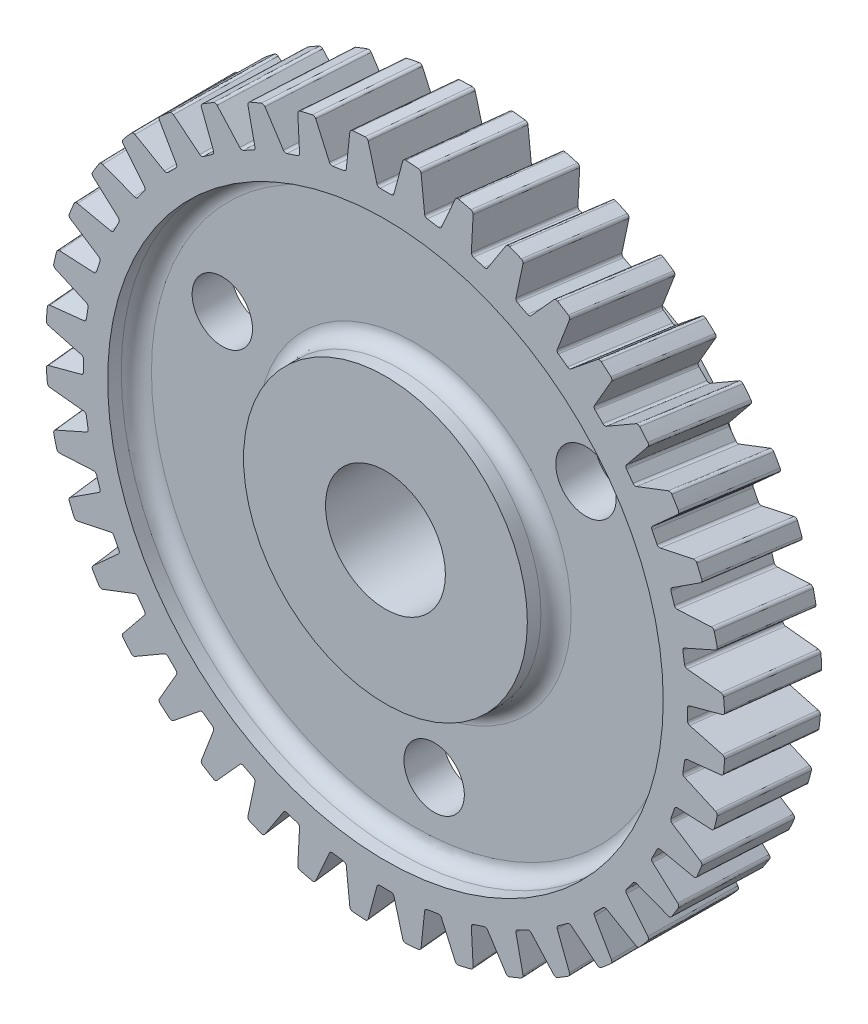
SolidWorks part; units mm, degrees
ref_plane "Front Plane" through (0, 0, 0) normal (0, 0, 1) x (1, 0, 0)
ref_plane "Top Plane" through (0, 0, 0) normal (0, 1, 0) x (1, 0, 0)
ref_plane "Right Plane" through (0, 0, 0) normal (1, 0, 0) x (0, 0, -1)
sketch "Sketch2" plane through (0, 0, 0) normal (1, 0, 0) x (0, 0, -1)
  line L0 (0, 0) -> (0, 22.5) construction
  line L1 (11, 3.9688) -> (-3.2, 3.9687)
  line L2 (-3.2, 3.9687) -> (-3.2, 9.4)
  line L3 (-3.2, 9.4) -> (-1.3, 9.4)
  line L4 (-1.3, 9.4) -> (-1.3, 18.4)
  line L5 (-1.3, 18.4) -> (-3.2, 18.4)
  line L6 (-3.2, 18.4) -> (-3.2, 22.5)
  line L7 (-3.2, 22.5) -> (3.2, 22.5)
  line L8 (3.2, 18.4) -> (3.2, 22.5)
  line L9 (1.3, 18.4) -> (3.2, 18.4)
  line L10 (1.3, 9.4) -> (1.3, 18.4)
  line L11 (3.2, 9.4) -> (1.3, 9.4)
  line L12 (3.2, 9.4) -> (11, 9.4)
  line L13 (11, 9.4) -> (11, 3.9688)
  line L14 (0, 0) -> (14.174, 0) construction
  dimension "D1" = 14.2
  dimension "D2" = 3.2
  dimension "D3" = 4.5
  dimension "D4" = 7.9375
  dimension "D5" = 9.4
  dimension "D6" = 9
  dimension "D7" = 22.5
  dimension "D8" = 6.4
revolve "Revolve1" add sketch "Sketch2" angle 360 about L14
fillet "Fillet1" radius 1 4 edges at (18.4, 0, 1.3) (9.4, 0, 1.3) (9.4, 0, -1.3) (18.4, 0, -1.3)
sketch "Sketch3" plane through (0, 0, 3.2) normal (0, 0, 1) x (1, 0, 0)
  line L0 (0, 22.6922) -> (0, 20) construction
  line L1 (-0.525, 20) -> (0.525, 20)
  line L2 (0.525, 20) -> (1.2464, 22.6922)
  line L3 (1.2464, 22.6922) -> (-1.2464, 22.6922)
  line L4 (-0.525, 20) -> (-1.2464, 22.6922)
  dimension "D1" = 20
  dimension "D2" = 1.05
  dimension "D3" = 15
sketch "Sketch4" plane through (0, 0, 0) normal (0, 1, 0) x (1, 0, 0)
  line L0 (0, -3.2) -> (0.691, 3.2)
  line L1 (1.2464, -3.2) -> (-1.2464, -3.2) construction
  line L2 (22.5, 3.2) -> (-22.5, 3.2) construction
sweep "Cut-Sweep1" cut profiles "Sketch3" path "Sketch4"
pattern_circular "CirPattern1" count 40 over 360 about axis through (0, 0, 3.2) along (0, 0, 1) of "Cut-Sweep1"
fillet "Fillet2" radius 0.2 160 edges at (1.526, 22.4482, 0.0047) (0.8705, 20, 0) (-0.8445, 22.4841, -0.0056) (-2.0045, 22.4105, 0.0047) (-2.2689, 19.8899, 0) (-3.306, 19.7257, 0) (-4.3514, 22.0752, -0.0056) (-5.4856, 21.8211, 0.0047) (-5.3525, 19.2901, 0) (-6.3511, 18.9657, 0) (-7.7512, 21.1227, -0.0056) (-8.8316, 20.6943, 0.0047) (-8.3042, 18.2153, 0) (-9.2398, 17.7386, 0) (-10.9601, 19.6501, -0.0056) (-11.9602, 19.0579, 0.0047) (-11.0515, 16.692, 0) (-11.9009, 16.0748, 0) (-13.8991, 17.6936, -0.0056) (-14.7943, 16.9523, 0.0047) (-13.5266, 14.7577, 0) (-14.2691, 14.0152, 0) (-16.4959, 15.3015, -0.0056) (-17.264, 14.4292, 0.0047) (-15.6687, 12.4599, 0) (-16.2859, 11.6105, 0) (-18.6865, 12.5326, -0.0056) (-19.3087, 11.5509, 0.0047) (-17.4249, 9.8554, 0) (-17.9016, 8.9199, 0) (-20.4169, 9.4551, -0.0056) (-20.878, 8.3882, 0.0047) (-18.7521, 7.0082, 0) (-19.0766, 6.0096, 0) (-21.6447, 6.1448, -0.0056) (-21.9331, 5.0188, 0.0047) (-19.6176, 3.9885, 0) (-19.7818, 2.9514, 0) (-22.3394, 2.6832, -0.0056) (-22.4482, 1.526, 0.0047) (-20, 0.8705, 0) (-20, -0.1795, 0) (-22.4841, -0.8445, -0.0056) (-22.4105, -2.0045, 0.0047) (-19.8899, -2.2689, 0) (-19.7257, -3.306, 0) (-22.0752, -4.3514, -0.0056) (-21.8211, -5.4856, 0.0047) (-19.2901, -5.3525, 0) (-18.9657, -6.3511, 0) (-21.1227, -7.7512, -0.0056) (-20.6943, -8.8316, 0.0047) (-18.2153, -8.3042, 0) (-17.7386, -9.2398, 0) (-19.6501, -10.9601, -0.0056) (-19.0579, -11.9602, 0.0047) (-16.692, -11.0515, 0) (-16.0748, -11.9009, 0) (-17.6936, -13.8991, -0.0056) (-16.9523, -14.7943, 0.0047) (-14.7577, -13.5266, 0) (-14.0152, -14.2691, 0) (-15.3015, -16.4959, -0.0056) (-14.4292, -17.264, 0.0047) (-12.4599, -15.6687, 0) (-11.6105, -16.2859, 0) (-12.5326, -18.6865, -0.0056) (-11.5509, -19.3087, 0.0047) (-9.8554, -17.4249, 0) (-8.9199, -17.9016, 0) (-9.4551, -20.4169, -0.0056) (-8.3882, -20.878, 0.0047) (-7.0082, -18.7521, 0) (-6.0096, -19.0766, 0) (-6.1448, -21.6447, -0.0056) (-5.0188, -21.9331, 0.0047) (-3.9885, -19.6176, 0) (-2.9514, -19.7818, 0) (-2.6832, -22.3394, -0.0056) (-1.526, -22.4482, 0.0047) (-0.8705, -20, 0) (0.1795, -20, 0) (0.8445, -22.4841, -0.0056) (2.0045, -22.4105, 0.0047) (2.2689, -19.8899, 0) (3.306, -19.7257, 0) (4.3514, -22.0752, -0.0056) (5.4856, -21.8211, 0.0047) (5.3525, -19.2901, 0) (6.3511, -18.9657, 0) (7.7512, -21.1227, -0.0056) (8.8316, -20.6943, 0.0047) (8.3042, -18.2153, 0) (9.2398, -17.7386, 0) (10.9601, -19.6501, -0.0056) (11.9602, -19.0579, 0.0047) (11.0515, -16.692, 0) (11.9009, -16.0748, 0) (13.8991, -17.6936, -0.0056) (14.7943, -16.9523, 0.0047) (13.5266, -14.7577, 0) (14.2691, -14.0152, 0) (16.4959, -15.3015, -0.0056) (17.264, -14.4292, 0.0047) (15.6687, -12.4599, 0) (16.2859, -11.6105, 0) (18.6865, -12.5326, -0.0056) (19.3087, -11.5509, 0.0047) (17.4249, -9.8554, 0) (17.9016, -8.9199, 0) (20.4169, -9.4551, -0.0056) (20.878, -8.3882, 0.0047) (18.7521, -7.0082, 0) (19.0766, -6.0096, 0) (21.6447, -6.1448, -0.0056) (21.9331, -5.0188, 0.0047) (19.6176, -3.9885, 0) (19.7818, -2.9514, 0) (22.3394, -2.6832, -0.0056) (22.4482, -1.526, 0.0047) (20, -0.8705, 0) (20, 0.1795, 0) (22.4841, 0.8445, -0.0056) (22.4105, 2.0045, 0.0047) (19.8899, 2.2689, 0) (19.7257, 3.306, 0) (22.0752, 4.3514, -0.0056) (21.8211, 5.4856, 0.0047) (19.2901, 5.3525, 0) (18.9657, 6.3511, 0) (21.1227, 7.7512, -0.0056) (20.6943, 8.8316, 0.0047) (18.2153, 8.3042, 0) (17.7386, 9.2398, 0) (19.6501, 10.9601, -0.0056) (19.0579, 11.9602, 0.0047) (16.692, 11.0515, 0) (16.0748, 11.9009, 0) (17.6936, 13.8991, -0.0056) (16.9523, 14.7943, 0.0047) (14.7577, 13.5266, 0) (14.0152, 14.2691, 0) (15.3015, 16.4959, -0.0056) (14.4292, 17.264, 0.0047) (12.4599, 15.6687, 0) (11.6105, 16.2859, 0) (12.5326, 18.6865, -0.0056) (11.5509, 19.3087, 0.0047) (9.8554, 17.4249, 0) (8.9199, 17.9016, 0) (9.4551, 20.4169, -0.0056) (8.3882, 20.878, 0.0047) (7.0082, 18.7521, 0) (6.0096, 19.0766, 0) (6.1448, 21.6447, -0.0056) (5.0188, 21.9331, 0.0047) (3.9885, 19.6176, 0) (2.9514, 19.7818, 0) (2.6832, 22.3394, -0.0056) (-0.1795, 20, 0)
ref_axis "gear axis" through (0, 0, -11) along (0, 0, 1)
hole_wizard "Ø4.0 (4) Diameter Hole1" positions "Sketch5" profile "Sketch6" hole size "Ø4.0" standard "ISO" end condition through all
sketch "Sketch5" plane through (59.759, -178.203, 3.9366) normal (0, 0, 1) x (1, -0.0054, 0)
  circle A5 centre (-60.718, 177.8786) radius 13.9687
  point P0 (-73.4549, 183.6142)
  point P2 (-49.3823, 186.0412)
  point P4 (-59.3167, 163.9803)
sketch "Sketch6" plane through (-12.7058, 5.8041, 3.9366) normal (1, 0, 0) x (0, -1, 0)
  line L0 (0, 0) -> (0, 14.9366)
  line L1 (0, 14.9366) -> (2, 14.9366)
  line L2 (2, 14.9366) -> (2, 0)
  line L3 (2, 0) -> (0, 0)
  line L4 (0, -6.35) -> (0, 107.95) construction
  dimension "Thru Hole Dia." = 4
  dimension "Thru Hole Depth" = 14.9366
